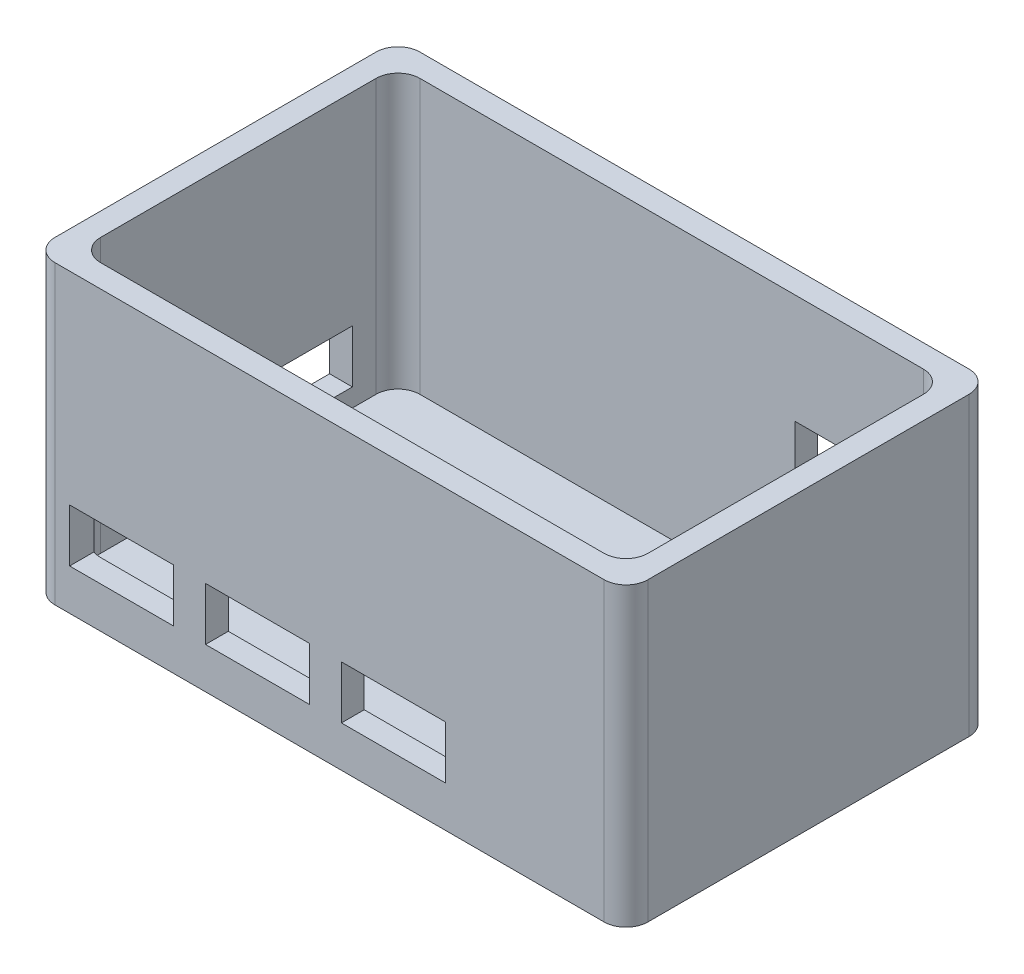
SolidWorks part; units mm, degrees
ref_plane "Front Plane" through (0, 0, 0) normal (0, 0, 1) x (1, 0, 0)
ref_plane "Top Plane" through (0, 0, 0) normal (0, 1, 0) x (1, 0, 0)
ref_plane "Right Plane" through (0, 0, 0) normal (1, 0, 0) x (0, 0, -1)
sketch "Sketch1" plane through (0, 0, 0) normal (0, 1, 0) x (1, 0, 0)
  line L1 (0, 0) -> (76.2, 0)
  line L2 (0, 0) -> (0, -44.45)
  line L3 (0, -44.45) -> (76.2, -44.45)
  line L4 (76.2, 0) -> (76.2, -44.45)
  dimension "D1" = 76.2
  dimension "D2" = 44.45
extrude "Boss-Extrude1" add sketch "Sketch1" along normal blind 38.1
shell "Shell1" thickness 3.175 removed face at (38.1, 38.1, 22.225) outward yes
sketch "Sketch2" plane through (0, 0, 47.625) normal (0, 0, 1) x (1, 0, 0)
  line L0 (0, 0) -> (76.2, 0) construction
  line L1 (39.751, 9.906) -> (54.229, 9.906)
  line L2 (39.751, 9.906) -> (39.751, 2.54)
  line L3 (39.751, 2.54) -> (54.229, 2.54)
  line L4 (54.229, 9.906) -> (54.229, 2.54)
  line L6 (1.905, 9.906) -> (16.383, 9.906)
  line L7 (1.905, 9.906) -> (1.905, 2.54)
  line L8 (1.905, 2.54) -> (16.383, 2.54)
  line L9 (16.383, 9.906) -> (16.383, 2.54)
  line L10 (20.828, 9.906) -> (35.306, 9.906)
  line L11 (20.828, 9.906) -> (20.828, 2.54)
  line L12 (20.828, 2.54) -> (35.306, 2.54)
  line L13 (35.306, 9.906) -> (35.306, 2.54)
  dimension "D1" = 7.366
  dimension "D2" = 14.478
  dimension "D3" = 2.54
  dimension "D4" = 4.445
  dimension "D5" = 4.445
  dimension "D6" = 1.905
extrude "Cut-Extrude1" cut sketch "Sketch2" against normal blind 12.7
sketch "Sketch3" plane through (-3.175, 0, 0) normal (-1, 0, 0) x (0, 0, 1)
  line L0 (44.45, 38.1) -> (44.45, 0) construction
  line L1 (6.35, 9.906) -> (31.75, 9.906)
  line L2 (6.35, 9.906) -> (6.35, 2.54)
  line L3 (6.35, 2.54) -> (31.75, 2.54)
  line L4 (31.75, 9.906) -> (31.75, 2.54)
  line L5 (0, 0) -> (44.45, 0) construction
  dimension "D1" = 25.4
  dimension "D2" = 7.366
  dimension "D3" = 12.7
  dimension "D4" = 2.54
extrude "Cut-Extrude2" cut sketch "Sketch3" against normal blind 12.7
sketch "Sketch4" plane through (0, 0, -3.175) normal (0, 0, -1) x (-1, 0, 0)
  line L0 (-76.2, 38.1) -> (-76.2, 0) construction
  line L1 (-69.85, 22.86) -> (-55.245, 22.86)
  line L2 (-69.85, 22.86) -> (-69.85, 3.81)
  line L3 (-69.85, 3.81) -> (-55.245, 3.81)
  line L4 (-55.245, 22.86) -> (-55.245, 3.81)
  line L5 (-76.2, 0) -> (0, 0) construction
  dimension "D1" = 19.05
  dimension "D2" = 14.605
  dimension "D3" = 6.35
  dimension "D4" = 3.81
extrude "Cut-Extrude3" cut sketch "Sketch4" against normal blind 12.7
fillet "Fillet1" radius 3.048 8 edges at (0, 19.05, 0) (-3.175, 17.4625, -3.175) (0, 19.05, 44.45) (-3.175, 17.4625, 47.625) (79.375, 17.4625, 47.625) (76.2, 19.05, 44.45) (76.2, 19.05, 0) (79.375, 17.4625, -3.175)
